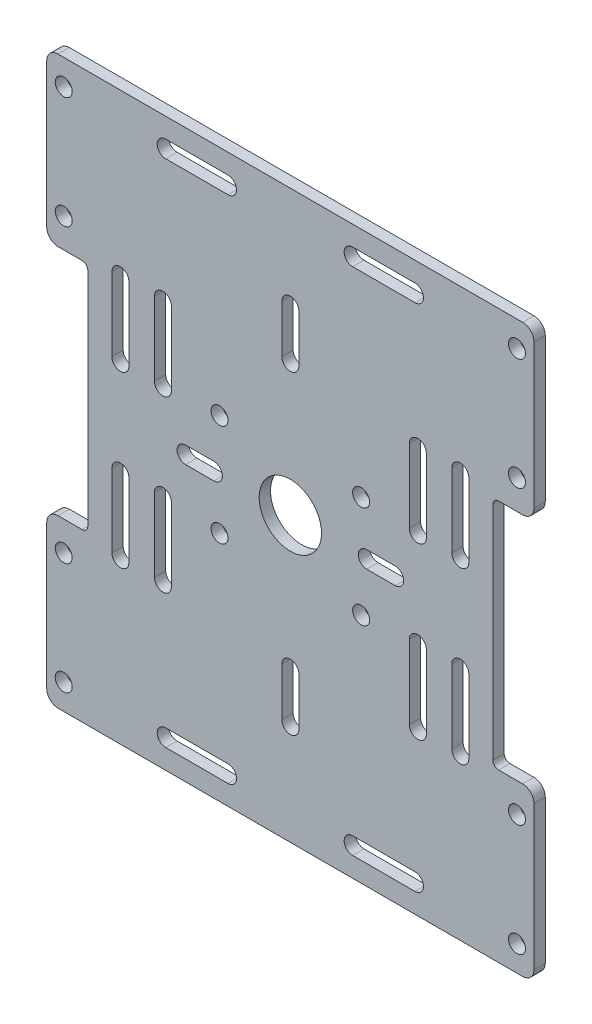
SolidWorks part; units mm, degrees
ref_plane "前基準面" through (0, 0, 0) normal (0, 0, 1) x (1, 0, 0)
ref_plane "上基準面" through (0, 0, 0) normal (0, 1, 0) x (1, 0, 0)
ref_plane "右基準面" through (0, 0, 0) normal (1, 0, 0) x (0, 0, -1)
sketch "草圖1" plane through (0, 0, 0) normal (0, 0, 1) x (1, 0, 0)
  line L0 (-13.5, 0) -> (-18.5, 0) construction
  line L3 (13.5, 0) -> (18.5, 0) construction
  line L4 (13.5, 1.5) -> (18.5, 1.5)
  line L5 (13.5, -1.5) -> (18.5, -1.5)
  line L6 (22.5, -8.5) -> (22.5, -21.5) construction
  line L7 (24, -8.5) -> (24, -21.5)
  line L8 (21, -8.5) -> (21, -21.5)
  line L9 (30, -8.5) -> (30, -21.5) construction
  line L12 (-167.459, 0) -> (250.2577, 0) construction
  line L13 (0, 741.9689) -> (0, -704.7384) construction
  line L14 (31.5, -8.5) -> (31.5, -21.5)
  line L15 (28.5, -8.5) -> (28.5, -21.5)
  line L16 (30, 8.5) -> (30, 21.5) construction
  line L17 (31.5, 8.5) -> (31.5, 21.5)
  line L18 (28.5, 8.5) -> (28.5, 21.5)
  line L19 (22.5, 8.5) -> (22.5, 21.5) construction
  line L20 (24, 8.5) -> (24, 21.5)
  line L21 (21, 8.5) -> (21, 21.5)
  line L22 (-22.5, 8.5) -> (-22.5, 21.5) construction
  line L23 (-24, 8.5) -> (-24, 21.5)
  line L24 (-21, 8.5) -> (-21, 21.5)
  line L25 (-30, 8.5) -> (-30, 21.5) construction
  line L26 (-31.5, 8.5) -> (-31.5, 21.5)
  line L27 (-28.5, 8.5) -> (-28.5, 21.5)
  line L28 (-30, -8.5) -> (-30, -21.5) construction
  line L29 (-31.5, -8.5) -> (-31.5, -21.5)
  line L30 (-28.5, -8.5) -> (-28.5, -21.5)
  line L31 (-22.5, -8.5) -> (-22.5, -21.5) construction
  line L32 (-24, -8.5) -> (-24, -21.5)
  line L33 (-21, -8.5) -> (-21, -21.5)
  line L34 (-22, -45) -> (-11, -45) construction
  line L35 (-22, -43.5) -> (-11, -43.5)
  line L36 (-22, -46.5) -> (-11, -46.5)
  line L37 (22, -45) -> (11, -45) construction
  line L38 (22, -43.5) -> (11, -43.5)
  line L39 (22, -46.5) -> (11, -46.5)
  line L40 (22, 45) -> (11, 45) construction
  line L41 (22, 43.5) -> (11, 43.5)
  line L42 (22, 46.5) -> (11, 46.5)
  line L43 (-22, 45) -> (-11, 45) construction
  line L44 (-22, 43.5) -> (-11, 43.5)
  line L45 (-22, 46.5) -> (-11, 46.5)
  line L46 (-35.75, -20.5625) -> (-43, -20.5625)
  line L47 (-25.75, -50) -> (25.75, -50)
  line L48 (-35.75, -20.5625) -> (-35.75, 20.5625)
  line L49 (-25.75, 50) -> (25.75, 50)
  line L50 (35.75, -20.5625) -> (35.75, 20.5625)
  line L51 (-35.75, -50) -> (35.75, 50) construction
  line L52 (-35.75, 50) -> (35.75, -50) construction
  line L53 (-13.5, 1.5) -> (-18.5, 1.5)
  line L54 (-13.5, -1.5) -> (-18.5, -1.5)
  line L55 (0, -23.5) -> (0, -32) construction
  line L56 (1.5, -23.5) -> (1.5, -32)
  line L57 (-1.5, -23.5) -> (-1.5, -32)
  line L58 (0, 23.5) -> (0, 32) construction
  line L59 (1.5, 23.5) -> (1.5, 32)
  line L60 (-1.5, 23.5) -> (-1.5, 32)
  line L61 (-43, -20.5625) -> (-43, -50)
  line L62 (-43, -50) -> (-25.75, -50)
  line L63 (43, -50) -> (25.75, -50)
  line L64 (43, -20.5625) -> (43, -50)
  line L65 (35.75, -20.5625) -> (43, -20.5625)
  line L66 (35.75, 20.5625) -> (43, 20.5625)
  line L67 (43, 20.5625) -> (43, 50)
  line L68 (43, 50) -> (25.75, 50)
  line L69 (-43, 50) -> (-25.75, 50)
  line L70 (-43, 20.5625) -> (-43, 50)
  line L71 (-35.75, 20.5625) -> (-43, 20.5625)
  circle A0 centre (0, 0) radius 5.5
  circle A4 centre (12.5, -9) radius 1.5
  arc A7 (13.5, 1.5) -> (13.5, -1.5) centre (13.5, 0) ccw
  arc A8 (18.5, -1.5) -> (18.5, 1.5) centre (18.5, 0) ccw
  arc A9 (24, -8.5) -> (21, -8.5) centre (22.5, -8.5) ccw
  arc A10 (21, -21.5) -> (24, -21.5) centre (22.5, -21.5) ccw
  arc A13 (31.5, -8.5) -> (28.5, -8.5) centre (30, -8.5) ccw
  arc A14 (28.5, -21.5) -> (31.5, -21.5) centre (30, -21.5) ccw
  arc A15 (31.5, 8.5) -> (28.5, 8.5) centre (30, 8.5) cw
  arc A16 (28.5, 21.5) -> (31.5, 21.5) centre (30, 21.5) cw
  arc A17 (24, 8.5) -> (21, 8.5) centre (22.5, 8.5) cw
  arc A18 (21, 21.5) -> (24, 21.5) centre (22.5, 21.5) cw
  arc A19 (-24, 8.5) -> (-21, 8.5) centre (-22.5, 8.5) ccw
  arc A20 (-21, 21.5) -> (-24, 21.5) centre (-22.5, 21.5) ccw
  arc A21 (-31.5, 8.5) -> (-28.5, 8.5) centre (-30, 8.5) ccw
  arc A22 (-28.5, 21.5) -> (-31.5, 21.5) centre (-30, 21.5) ccw
  arc A23 (-31.5, -8.5) -> (-28.5, -8.5) centre (-30, -8.5) cw
  arc A24 (-28.5, -21.5) -> (-31.5, -21.5) centre (-30, -21.5) cw
  arc A25 (-24, -8.5) -> (-21, -8.5) centre (-22.5, -8.5) cw
  arc A26 (-21, -21.5) -> (-24, -21.5) centre (-22.5, -21.5) cw
  arc A27 (-22, -43.5) -> (-22, -46.5) centre (-22, -45) ccw
  arc A28 (-11, -46.5) -> (-11, -43.5) centre (-11, -45) ccw
  arc A29 (22, -43.5) -> (22, -46.5) centre (22, -45) cw
  arc A30 (11, -46.5) -> (11, -43.5) centre (11, -45) cw
  arc A31 (22, 43.5) -> (22, 46.5) centre (22, 45) ccw
  arc A32 (11, 46.5) -> (11, 43.5) centre (11, 45) ccw
  arc A33 (-22, 43.5) -> (-22, 46.5) centre (-22, 45) cw
  arc A34 (-11, 46.5) -> (-11, 43.5) centre (-11, 45) cw
  arc A39 (-13.5, 1.5) -> (-13.5, -1.5) centre (-13.5, 0) cw
  arc A40 (-18.5, -1.5) -> (-18.5, 1.5) centre (-18.5, 0) cw
  circle A41 centre (-12.5, -9) radius 1.5
  circle A42 centre (12.5, 9) radius 1.5
  circle A43 centre (-12.5, 9) radius 1.5
  arc A44 (1.5, -23.5) -> (-1.5, -23.5) centre (0, -23.5) ccw
  arc A45 (-1.5, -32) -> (1.5, -32) centre (0, -32) ccw
  arc A46 (1.5, 23.5) -> (-1.5, 23.5) centre (0, 23.5) cw
  arc A47 (-1.5, 32) -> (1.5, 32) centre (0, 32) cw
  circle A48 centre (-40, -25.75) radius 1.5
  circle A49 centre (40, -25.75) radius 1.5
  circle A50 centre (40, 25.75) radius 1.5
  circle A51 centre (-40, 25.75) radius 1.5
  circle A52 centre (-40, -45.5) radius 1.5
  circle A53 centre (-40, 45.5) radius 1.5
  circle A54 centre (40, 45.5) radius 1.5
  circle A55 centre (40, -45.5) radius 1.5
  point P5 (0, -27.75)
  point P8 (-16, 0)
  point P18 (16, 0)
  point P25 (22.5, -15)
  point P34 (30, -15)
  point P45 (30, 15)
  point P52 (22.5, 15)
  point P59 (-22.5, 15)
  point P66 (-30, 15)
  point P73 (-30, -15)
  point P80 (-22.5, -15)
  point P87 (-16.5, -45)
  point P94 (16.5, -45)
  point P101 (16.5, 45)
  point P108 (-16.5, 45)
  point P140 (0, 27.75)
  dimension "D2" = 11
  dimension "D3" = 3
  dimension "D4" = 5
  dimension "D6" = 1.5
  dimension "D9" = 23.5
  dimension "D10" = 1.5
  dimension "D11" = 1.5
  dimension "D12" = 1.5
  dimension "D13" = 8.5
  dimension "D20" = 8.5
  dimension "D24" = 1.5
  dimension "D21" = 45
  dimension "D5" = 2.5
  dimension "D25" = 51.5
  dimension "D27" = 3
  dimension "D28" = 45.5
  dimension "D29" = 3
  dimension "D7" = 12.5
  dimension "D8" = 9
  dimension "D14" = 60
  dimension "D15" = 7.5
  dimension "D16" = 71.5
  dimension "D17" = 100
  dimension "D18" = 13
  dimension "D19" = 13
  dimension "D22" = 22
  dimension "D23" = 11
  dimension "D26" = 40
  dimension "D30" = 43
extrude "填料-伸長1" add sketch "草圖1" along normal blind 2
fillet "圓角1" radius 1 4 edges at (35.75, -20.5625, 1) (35.75, 20.5625, 1) (-35.75, 20.5625, 1) (-35.75, -20.5625, 1)
fillet "圓角2" radius 2 8 edges at (43, 20.5625, 1) (43, 50, 1) (-43, 50, 1) (-43, 20.5625, 1) (-43, -20.5625, 1) (-43, -50, 1) (43, -50, 1) (43, -20.5625, 1)
